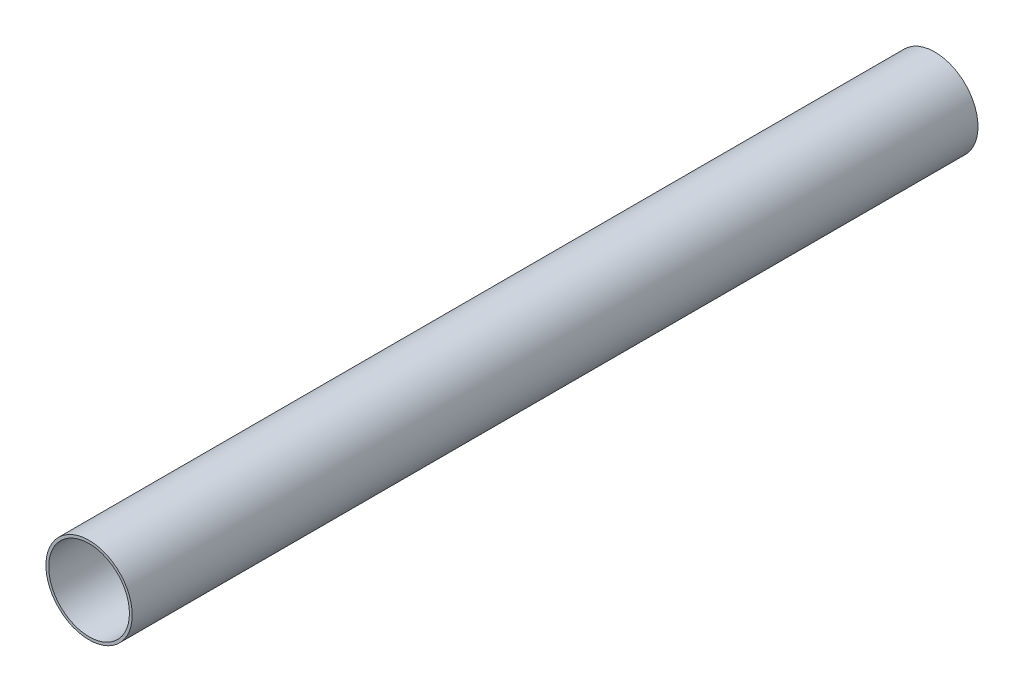
SolidWorks part; units mm, degrees
material "ASTM A53 Grade B"
ref_plane "Front Plane" through (0, 0, 0) normal (0, 0, 1) x (1, 0, 0)
ref_plane "Top Plane" through (0, 0, 0) normal (0, 1, 0) x (1, 0, 0)
ref_plane "Right Plane" through (0, 0, 0) normal (1, 0, 0) x (0, 0, -1)
sketch "Croquis1" plane through (0, 0, 0) normal (0, 0, 1) x (1, 0, 0)
  circle A0 centre (0, 0) radius 26.2509
  circle A1 centre (0, 0) radius 28.0509
  dimension "D1" = 52.5018
  dimension "D2" = 56.1018
extrude "Saliente-Extruir1" add sketch "Croquis1" against normal blind 550
equation "\"IDcase\"= 52.5018"
equation "\"D1@Croquis1\"=\"IDcase\""
equation "\"ODcase\"= \"IDcase\" + 2 * \"CaseThickness\""
equation "\"D2@Croquis1\"=\"ODcase\""
equation "\"CaseLength\"= 525mm + 25"
equation "\"D1@Saliente-Extruir1\"=\"CaseLength\""
equation "\"CaseThickness\" = 1.8mm"
